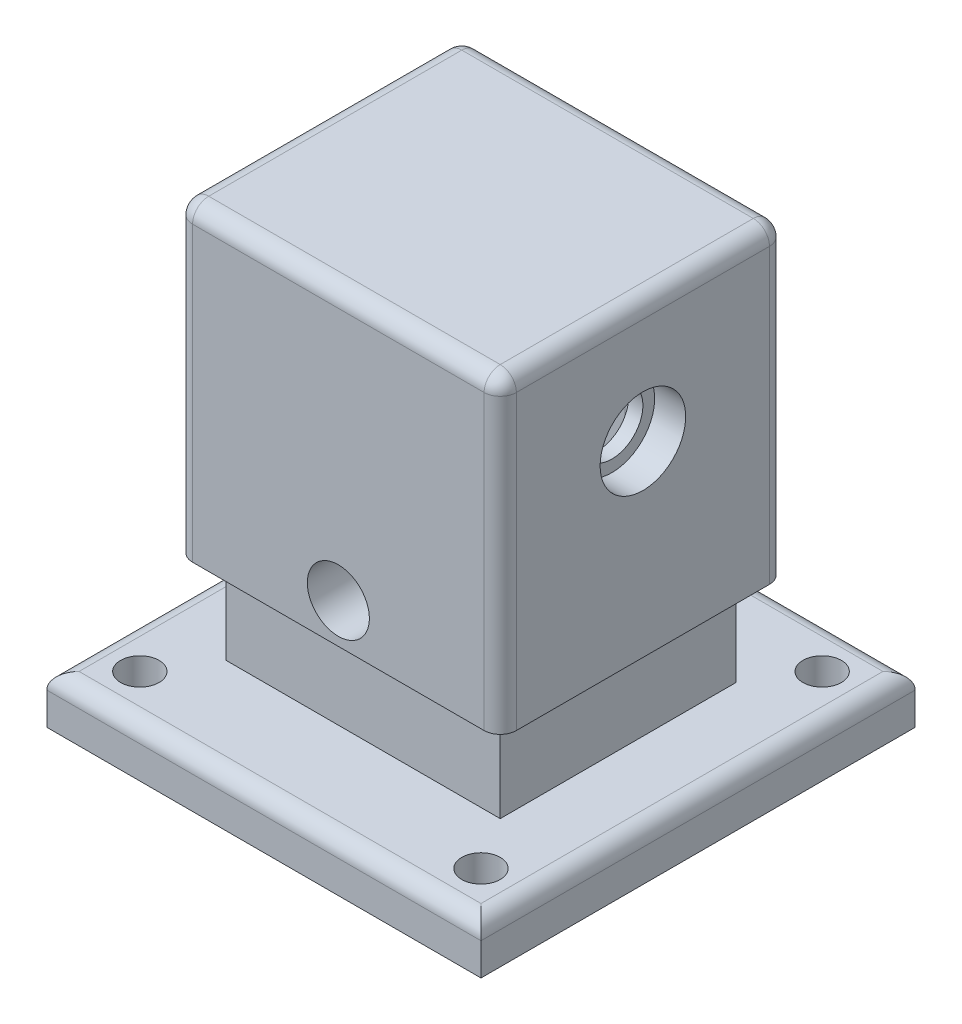
SolidWorks part; units mm, degrees
ref_plane "Front Plane" through (0, 0, 0) normal (0, 0, 1) x (1, 0, 0)
ref_plane "Top Plane" through (0, 0, 0) normal (0, 1, 0) x (1, 0, 0)
ref_plane "Right Plane" through (0, 0, 0) normal (1, 0, 0) x (0, 0, -1)
sketch "Sketch1" plane through (0, 0, 0) normal (0, 1, 0) x (1, 0, 0)
  line L0 (0, -44.45) -> (0, 44.45) construction
  line L1 (-44.45, -44.45) -> (44.45, -44.45)
  line L2 (-44.45, -44.45) -> (-44.45, 44.45)
  line L3 (-44.45, 44.45) -> (44.45, 44.45)
  line L4 (44.45, -44.45) -> (44.45, 44.45)
  line L5 (-44.45, -44.45) -> (44.45, 44.45) construction
  line L6 (-44.45, 44.45) -> (44.45, -44.45) construction
  circle A0 centre (-34.925, 34.925) radius 3.937
  circle A1 centre (-34.925, -34.925) radius 3.937
  circle A2 centre (34.925, 34.925) radius 3.937
  circle A3 centre (34.925, -34.925) radius 3.937
  point P0 (0, 0)
  point P17 (0, 0)
  dimension "D3" = 69.85
  dimension "D4" = 69.85
  dimension "D5" = 7.874
  dimension "D1" = 88.9
  dimension "D2" = 88.9
extrude "Boss-Extrude1" add sketch "Sketch1" along normal blind 9.906
sketch "Sketch2" plane through (0, 9.906, 0) normal (0, 1, 0) x (1, 0, 0)
  line L1 (-28.067, -24.13) -> (28.067, -24.13)
  line L2 (-28.067, -24.13) -> (-28.067, 24.13)
  line L3 (-28.067, 24.13) -> (28.067, 24.13)
  line L4 (28.067, -24.13) -> (28.067, 24.13)
  line L5 (-28.067, -24.13) -> (28.067, 24.13) construction
  line L6 (-28.067, 24.13) -> (28.067, -24.13) construction
  point P0 (0, 0)
  dimension "D1" = 48.26
  dimension "D2" = 56.134
extrude "Boss-Extrude2" add sketch "Sketch2" along normal blind 19.05
sketch "Sketch3" plane through (0, 28.956, 0) normal (0, 1, 0) x (1, 0, 0)
  line L1 (-33.147, -29.21) -> (33.147, -29.21)
  line L2 (-33.147, -29.21) -> (-33.147, 29.21)
  line L3 (-33.147, 29.21) -> (33.147, 29.21)
  line L4 (33.147, -29.21) -> (33.147, 29.21)
  line L5 (-33.147, -29.21) -> (33.147, 29.21) construction
  line L6 (-33.147, 29.21) -> (33.147, -29.21) construction
  point P0 (0, 0)
  dimension "D1" = 58.42
  dimension "D2" = 66.294
extrude "Boss-Extrude3" add sketch "Sketch3" along normal blind 63.246
sketch "Sketch4" plane through (0, 0, 0) normal (0, -1, 0) x (1, 0, 0)
  line L1 (-23.876, -12.7) -> (23.876, -12.7)
  line L2 (-23.876, -12.7) -> (-23.876, 12.7)
  line L3 (-23.876, 12.7) -> (23.876, 12.7)
  line L4 (23.876, -12.7) -> (23.876, 12.7)
  line L5 (-23.876, -12.7) -> (23.876, 12.7) construction
  line L6 (-23.876, 12.7) -> (23.876, -12.7) construction
  point P0 (0, 0)
  dimension "D1" = 25.4
  dimension "D2" = 47.752
extrude "Cut-Extrude1" cut sketch "Sketch4" against normal blind 76.2
sketch "Sketch5" plane through (0, 0, 0) normal (0, -1, 0) x (1, 0, 0)
  line L1 (-30.226, -19.05) -> (30.226, -19.05)
  line L2 (-30.226, -19.05) -> (-30.226, 19.05)
  line L3 (-30.226, 19.05) -> (30.226, 19.05)
  line L4 (30.226, -19.05) -> (30.226, 19.05)
  line L5 (-30.226, -19.05) -> (30.226, 19.05) construction
  line L6 (-30.226, 19.05) -> (30.226, -19.05) construction
  point P0 (0, 0)
  dimension "D1" = 60.452
  dimension "D2" = 38.1
extrude "Cut-Extrude2" cut sketch "Sketch5" against normal blind 3.302
sketch "Sketch6" plane through (-33.147, 0, 0) normal (-1, 0, 0) x (0, 0, 1)
  line L0 (-44.45, 0) -> (44.45, 0) construction
  line L1 (29.21, 92.202) -> (29.21, 28.956) construction
  circle A0 centre (0, 67.31) radius 6.35
  circle A1 centre (0, 67.31) radius 8.763
  dimension "D1" = 12.7
  dimension "D2" = 17.526
  dimension "D3" = 67.31
  dimension "D4" = 29.21
extrude "Cut-Extrude3" cut sketch "Sketch6" against normal through all contours A0 region at (-33.147, 67.31, 0)
extrude "Cut-Extrude4" cut sketch "Sketch6<3>" against normal blind 6.35 contours A1 A0 region at (-33.147, 67.31, -8.5151)
sketch "Sketch6<3>" plane through (-33.147, 0, 0) normal (-1, 0, 0) x (0, 0, 1) same geometry as "Sketch6"
mirror "Mirror1" about plane through (0, 0, 0) normal (1, 0, 0) of "Cut-Extrude4"
sketch "Sketch8" plane through (0, 0, -29.21) normal (0, 0, -1) x (-1, 0, 0)
  line L0 (-44.45, 0) -> (44.45, 0) construction
  circle A0 centre (0, 37.084) radius 6.35
  point P2 (0, 0)
  dimension "D2" = 12.7
  dimension "D1" = 37.084
extrude "Cut-Extrude5" cut sketch "Sketch8" against normal through all
fillet "Fillet1" radius 3.302 12 edges at (0, 92.202, 29.21) (-33.147, 92.202, 0) (0, 92.202, -29.21) (33.147, 92.202, 0) (-44.45, 9.906, 0) (0, 9.906, 44.45) (44.45, 9.906, 0) (0, 9.906, -44.45) (-33.147, 60.579, -29.21) (-33.147, 60.579, 29.21) (33.147, 60.579, 29.21) (33.147, 60.579, -29.21)
fillet "Fillet2" radius 3.302 4 edges at (-30.226, 1.651, -19.05) (30.226, 1.651, -19.05) (30.226, 1.651, 19.05) (-30.226, 1.651, 19.05)
fillet "Fillet3" radius 7.112 4 edges at (-23.876, 39.751, -12.7) (23.876, 39.751, -12.7) (23.876, 39.751, 12.7) (-23.876, 39.751, 12.7)
hole_wizard "#4-40 Tapped Hole2" positions "Sketch11" profile "Sketch12" tap size "#4-40" standard "ANSI Inch"
sketch "Sketch11" plane through (0, 3.302, 0) normal (0, -1, 0) x (-1, 0, 0)
  line L0 (0, -19.05) -> (0, 0) construction
  line L1 (-26.924, -19.05) -> (26.924, -19.05) construction
  line L2 (0, 0) -> (-30.226, 0) construction
  line L3 (-30.226, 15.748) -> (-30.226, -15.748) construction
  point P0 (26.289, -15.0884)
  point P2 (-26.289, -15.0884)
  point P4 (-26.289, 15.0884)
  point P6 (26.289, 15.0884)
  point P22 (0, 0)
  point P27 (-26.4147, 9.4627)
  dimension "D1" = 52.578
  dimension "D2" = 30.1768
sketch "Sketch12" plane through (-26.289, 3.302, 15.0884) normal (1, 0, 0) x (0, 0, -1)
  line L0 (0, 0) -> (0, 9.5692)
  line L1 (0, 9.5692) -> (1.1303, 8.89)
  line L2 (1.1303, 8.89) -> (1.1303, 0)
  line L5 (1.1303, 0) -> (0, 0)
  line L10 (0, 9.5692) -> (-1.1303, 8.89) construction
  line L11 (0, -6.35) -> (0, 107.95) construction
  dimension "Tap Drill Dia." = 2.2606
  dimension "Tap Drill Depth" = 8.89
  dimension "Drill Angle" = 118
cosmetic thread "Hole Thread5" parameters "D1"=5.588, "D2"=2.8448
cosmetic thread "Hole Thread6" parameters "D1"=5.588, "D2"=2.8448
cosmetic thread "Hole Thread7" parameters "D1"=5.588, "D2"=2.8448
cosmetic thread "Hole Thread8" parameters "D1"=5.588, "D2"=2.8448
